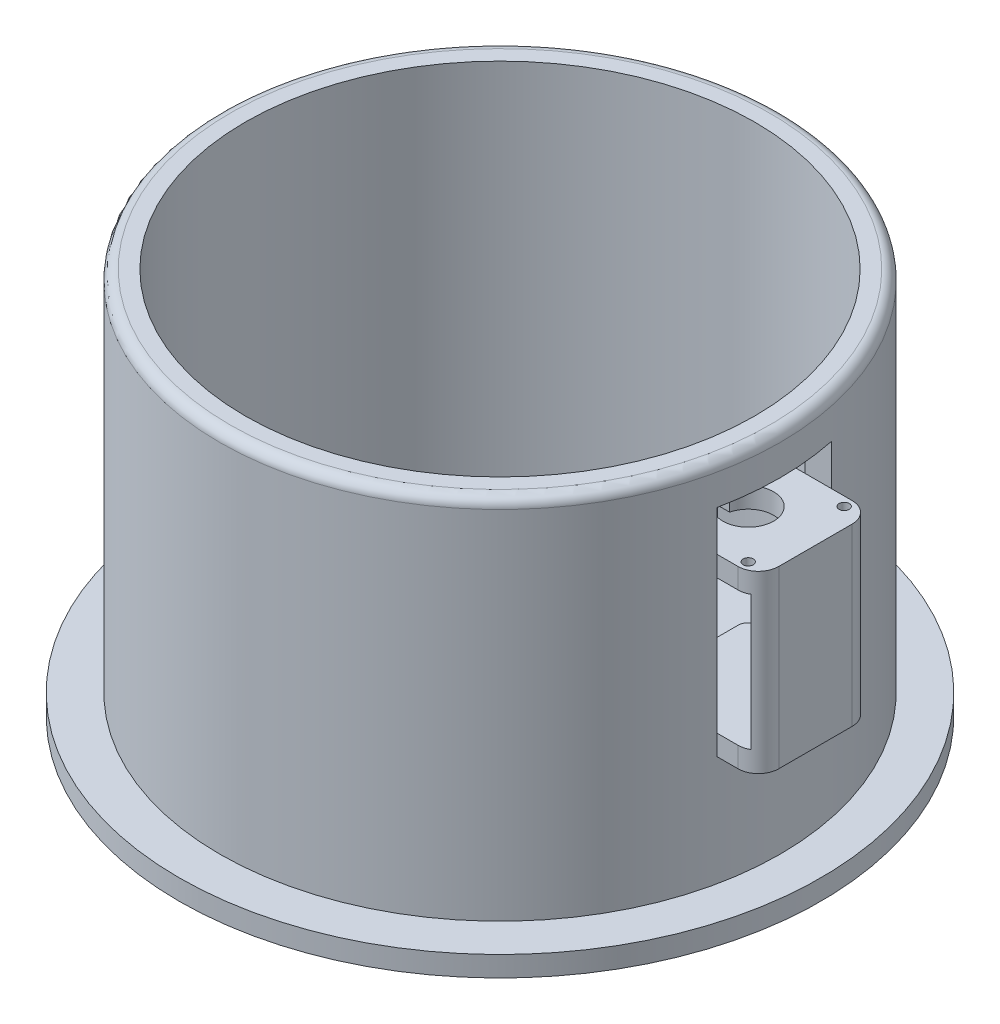
SolidWorks part; units mm, degrees
ref_plane "Front Plane" through (0, 0, 0) normal (0, 0, 1) x (1, 0, 0)
ref_plane "Top Plane" through (0, 0, 0) normal (0, 1, 0) x (1, 0, 0)
ref_plane "Right Plane" through (0, 0, 0) normal (1, 0, 0) x (0, 0, -1)
sketch "Sketch1" plane through (0, 0, 0) normal (0, 1, 0) x (1, 0, 0)
  circle A6 centre (0, 0) radius 125
  circle A7 centre (0, 0) radius 137.5
  dimension "D1" = 250
  dimension "D2" = 275
extrude "Boss-Extrude1" add sketch "Sketch1" along normal blind 180
sketch "Sketch2" plane through (0, 0, 0) normal (0, -1, 0) x (1, 0, 0)
  circle A0 centre (0, 0) radius 157.5
  dimension "D1" = 315
extrude "Boss-Extrude2" add sketch "Sketch2" along normal blind 10
sketch "Sketch3" plane through (0, 0, 0) normal (0, 1, 0) x (1, 0, 0)
  circle A0 centre (0, 0) radius 47.5
  circle A1 centre (0, 0) radius 52.5
  dimension "D1" = 95
  dimension "D2" = 105
extrude "Boss-Extrude3" add sketch "Sketch3" along normal blind 20
sketch "Sketch4" plane through (0, 0, 0) normal (1, 0, 0) x (0, 0, -1)
  line L0 (137.5, 180) -> (-137.5, 180) construction
  line L1 (-28, 160) -> (28, 160)
  line L2 (-28, 160) -> (-28, 64)
  line L3 (-28, 64) -> (28, 64)
  line L4 (28, 160) -> (28, 64)
  line L5 (-28, 160) -> (28, 64) construction
  line L6 (-28, 64) -> (28, 160) construction
  point P0 (0, 112)
  dimension "D1" = 56
  dimension "D2" = 96
  dimension "D3" = 20
extrude "Cut-Extrude4" cut sketch "Sketch4" along normal blind 150
sketch "Sketch5" plane through (0, 0, 28) normal (0, 0, -1) x (-1, 0, 0)
  line L1 (-149.8236, 140) -> (-93.8236, 140)
  line L2 (-149.8236, 140) -> (-149.8236, 130)
  line L3 (-149.8236, 130) -> (-93.8236, 130)
  line L4 (-93.8236, 140) -> (-93.8236, 130)
  line L5 (-149.8236, 140) -> (-93.8236, 130) construction
  line L6 (-149.8236, 130) -> (-93.8236, 140) construction
  line L7 (-137.5, 160) -> (-134.6189, 160) construction
  line L8 (-121.8236, 160) -> (-121.8236, 64) construction
  point P0 (-121.8236, 135)
  dimension "D1" = 10
  dimension "D2" = 25
  dimension "D3" = 56
extrude "Boss-Extrude4" add sketch "Sketch5" along normal up to surface (56 mm away) up to face at (128.2213, 112, -28)
sketch "Sketch6" plane through (0, 64, 0) normal (0, 1, 0) x (1, 0, 0)
  line L1 (93.8236, 28) -> (149.8236, 28)
  line L2 (93.8236, 28) -> (93.8236, -28)
  line L3 (93.8236, -28) -> (149.8236, -28)
  line L4 (149.8236, 28) -> (149.8236, -28)
extrude "Boss-Extrude5" add sketch "Sketch6" against normal blind 10
sketch "Sketch7" plane through (0, 140, 0) normal (0, 1, 0) x (1, 0, 0)
  line L1 (98.2736, 23.55) -> (145.3736, 23.55) construction
  line L2 (98.2736, 23.55) -> (98.2736, -23.55) construction
  line L3 (98.2736, -23.55) -> (145.3736, -23.55) construction
  line L4 (145.3736, 23.55) -> (145.3736, -23.55) construction
  line L5 (98.2736, 23.55) -> (145.3736, -23.55) construction
  line L6 (98.2736, -23.55) -> (145.3736, 23.55) construction
  circle A0 centre (98.2736, 23.55) radius 2.5
  circle A1 centre (145.3736, 23.55) radius 2.5
  circle A2 centre (98.2736, -23.55) radius 2.5
  circle A3 centre (145.3736, -23.55) radius 2.5
  circle A4 centre (121.8236, 0) radius 12.5
  point P0 (121.8236, 0)
  dimension "D3" = 25
  dimension "D4" = 5
  dimension "D1" = 47.1
  dimension "D2" = 47.1
extrude "Cut-Extrude5" cut sketch "Sketch7" against normal blind 10
sketch "Sketch8" plane through (149.8236, 0, 0) normal (1, 0, 0) x (0, 0, -1)
  line L1 (-28, 140) -> (28, 140)
  line L2 (-28, 140) -> (-28, 54)
  line L3 (-28, 54) -> (28, 54)
  line L4 (28, 140) -> (28, 54)
extrude "Boss-Extrude6" add sketch "Sketch8" along normal blind 5
fillet "Fillet1" radius 10 2 edges at (154.8236, 97, -28) (154.8236, 97, 28)
fillet "Fillet2" radius 5 4 edges at (93.8236, 59, -28) (93.8236, 59, 28) (93.8236, 135, 28) (93.8236, 135, -28)
sketch "Sketch9" plane through (0, 140, 0) normal (0, 1, 0) x (1, 0, 0)
  line L0 (93.8236, 23) -> (93.8236, -23) construction
  line L1 (77.9583, 3) -> (109.689, 3)
  line L2 (77.9583, 3) -> (77.9583, -3)
  line L3 (77.9583, -3) -> (109.689, -3)
  line L4 (109.689, 3) -> (109.689, -3)
  line L5 (77.9583, 3) -> (109.689, -3) construction
  line L6 (77.9583, -3) -> (109.689, 3) construction
  circle A0 centre (121.8236, 0) radius 12.5 construction
  point P0 (93.8236, 0)
  dimension "D1" = 6
extrude "Cut-Extrude6" cut sketch "Sketch9" against normal blind 10
fillet "Fillet3" radius 5 1 edges at (0, 180, 137.5)
sketch "Sketch10" plane through (0, 0, 0) normal (0, 1, 0) x (1, 0, 0)
  circle A0 centre (0, 0) radius 47.5
  dimension "D1" = 95
extrude "Cut-Extrude7" cut sketch "Sketch10" against normal blind 2
